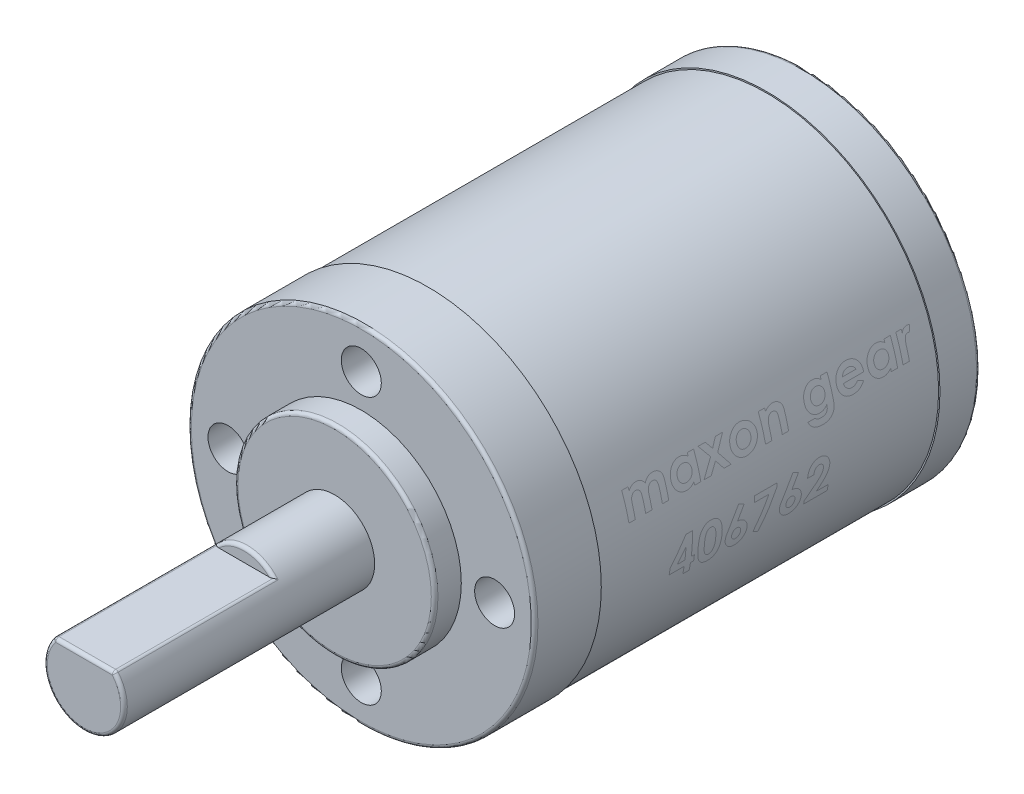
SolidWorks part; units mm, degrees
ref_plane "Plan de face" through (0, 0, 0) normal (0, 0, 1) x (1, 0, 0)
ref_plane "Plan de dessus" through (0, 0, 0) normal (0, 1, 0) x (1, 0, 0)
ref_plane "Plan de droite" through (0, 0, 0) normal (1, 0, 0) x (0, 0, -1)
sketch "Esquisse1" plane through (0, 0, 0) normal (1, 0, 0) x (0, 0, -1)
  line L0 (0, 0) -> (86.17, 0) construction
  line L1 (18.8, 3) -> (18.8, 7.5)
  line L2 (0, 0) -> (54.2, 0)
  line L3 (0, 0) -> (0, 3)
  line L4 (0, 3) -> (18.8, 3)
  line L5 (18.8, 7.5) -> (20.8, 7.5)
  line L6 (20.8, 7.5) -> (20.8, 13)
  line L7 (20.8, 13) -> (25.8, 13)
  line L8 (54.2, 13) -> (54.2, 0)
  line L9 (51.2, 13) -> (54.2, 13)
  line L11 (25.8, 13) -> (25.8, 12.9)
  line L12 (25.8, 12.9) -> (51.2, 12.9)
  line L13 (51.2, 13) -> (51.2, 12.9)
  dimension "D1" = 13
  dimension "D2" = 7.5
  dimension "D3" = 3
  dimension "D4" = 2
  dimension "D5" = 0.1
  dimension "D6" = 5
  dimension "D7" = 3
  dimension "D8" = 33.4
  dimension "D9" = 18.8
revolve "Révolution1" add sketch "Esquisse1" angle 360 about L0
sketch "Esquisse2" plane through (0, 0, -20.8) normal (0, 0, 1) x (1, 0, 0)
  line L0 (0, 10) -> (0, 0) construction
  circle A0 centre (0, 10) radius 1.5
  circle A1 centre (10, 0) radius 1.5
  circle A2 centre (0, -10) radius 1.5
  circle A3 centre (-10, 0) radius 1.5
  dimension "D1" = 3
  dimension "D2" = 10
  dimension "D3" = 4
extrude "Enlèv. mat.-Extru.1" cut sketch "Esquisse2" against normal blind 5
sketch "Esquisse3" plane through (0, 0, 0) normal (0, 0, 1) x (1, 0, 0)
  line L0 (-2.2361, 2) -> (2.2361, 2)
  circle A0 centre (0, 0) radius 3 construction
  arc A1 (-2.2361, 2) -> (2.2361, 2) centre (0, 0) cw
  dimension "D1" = 2
extrude "Enlèv. mat.-Extru.2" cut sketch "Esquisse3" against normal blind 12
fillet "Congé1" radius 0.25 8 edges at (13, 0, -54.2) (0, 3, -12) (-2.2361, 2, -6) (2.2361, 2, -6) (13, 0, -20.8) (7.5, 0, -18.8) (0, -3, 0) (0, 2, 0)
sketch "Esquisse4" plane through (0, 0, 0) normal (1, 0, 0) x (0, 0, -1)
  text T0 "<b>maxon gear</b>\r\n<b>   406762</b>" font "Century Gothic" height in points 10
wrap "Enroulement1" sketch "Esquisse4" wrap type scribe source sketch "Esquisse4" face at (12.9, 0, -25.8)
